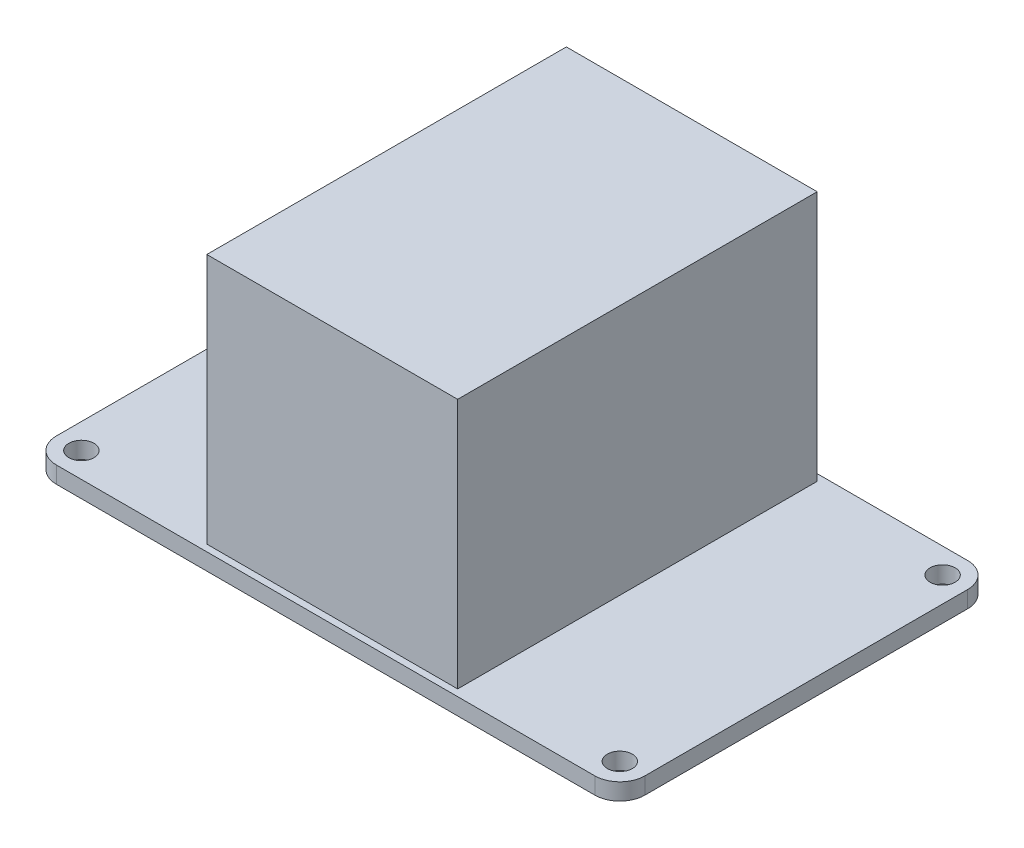
SolidWorks part; units mm, degrees
ref_plane "Front Plane" through (0, 0, 0) normal (0, 0, 1) x (1, 0, 0)
ref_plane "Top Plane" through (0, 0, 0) normal (0, 1, 0) x (1, 0, 0)
ref_plane "Right Plane" through (0, 0, 0) normal (1, 0, 0) x (0, 0, -1)
sketch "Sketch1" plane through (0, 0, 0) normal (0, 1, 0) x (1, 0, 0)
  line L1 (-35.2, -22.3) -> (35.2, -22.3)
  line L2 (-35.2, -22.3) -> (-35.2, 22.3)
  line L3 (-35.2, 22.3) -> (35.2, 22.3)
  line L4 (35.2, -22.3) -> (35.2, 22.3)
  line L5 (-35.2, -22.3) -> (35.2, 22.3) construction
  line L6 (-35.2, 22.3) -> (35.2, -22.3) construction
  point P0 (0, 0)
  dimension "D1" = 44.6
  dimension "D2" = 70.4
extrude "Boss-Extrude1" add sketch "Sketch1" along normal blind 2
sketch "Sketch3" plane through (0, 2, 0) normal (0, 1, 0) x (1, 0, 0)
  line L8 (32.2, -19.3) -> (32.2, 19.3)
  line L9 (32.2, 19.3) -> (-32.2, 19.3)
  line L10 (-32.2, 19.3) -> (-32.2, -19.3)
  line L11 (-32.2, -19.3) -> (32.2, -19.3)
  line L12 (32.2, -19.3) -> (32.2, 19.3) construction
  line L13 (32.2, 19.3) -> (-32.2, 19.3) construction
  line L14 (-32.2, 19.3) -> (-32.2, -19.3) construction
  line L15 (-32.2, -19.3) -> (32.2, -19.3) construction
  circle A0 centre (-32.2, 19.3) radius 1.5
  circle A1 centre (32.2, 19.3) radius 1.5
  circle A2 centre (32.2, -19.3) radius 1.5
  circle A3 centre (-32.2, -19.3) radius 1.5
  dimension "D2" = 3
  dimension "D1" = 3
extrude "Cut-Extrude1" cut sketch "Sketch3" against normal through all
fillet "Fillet1" radius 3 4 edges at (35.2, 1, -22.3) (35.2, 1, 22.3) (-35.2, 1, -22.3) (-35.2, 1, 22.3)
sketch "Sketch4" plane through (0, 2, 0) normal (0, 1, 0) x (1, 0, 0)
  line L1 (-15, -21.5) -> (15, -21.5)
  line L2 (-15, -21.5) -> (-15, 21.5)
  line L3 (-15, 21.5) -> (15, 21.5)
  line L4 (15, -21.5) -> (15, 21.5)
  line L5 (-15, -21.5) -> (15, 21.5) construction
  line L6 (-15, 21.5) -> (15, -21.5) construction
  point P0 (0, 0)
  dimension "D1" = 30
  dimension "D2" = 43
extrude "Boss-Extrude2" add sketch "Sketch4" along normal blind 30
